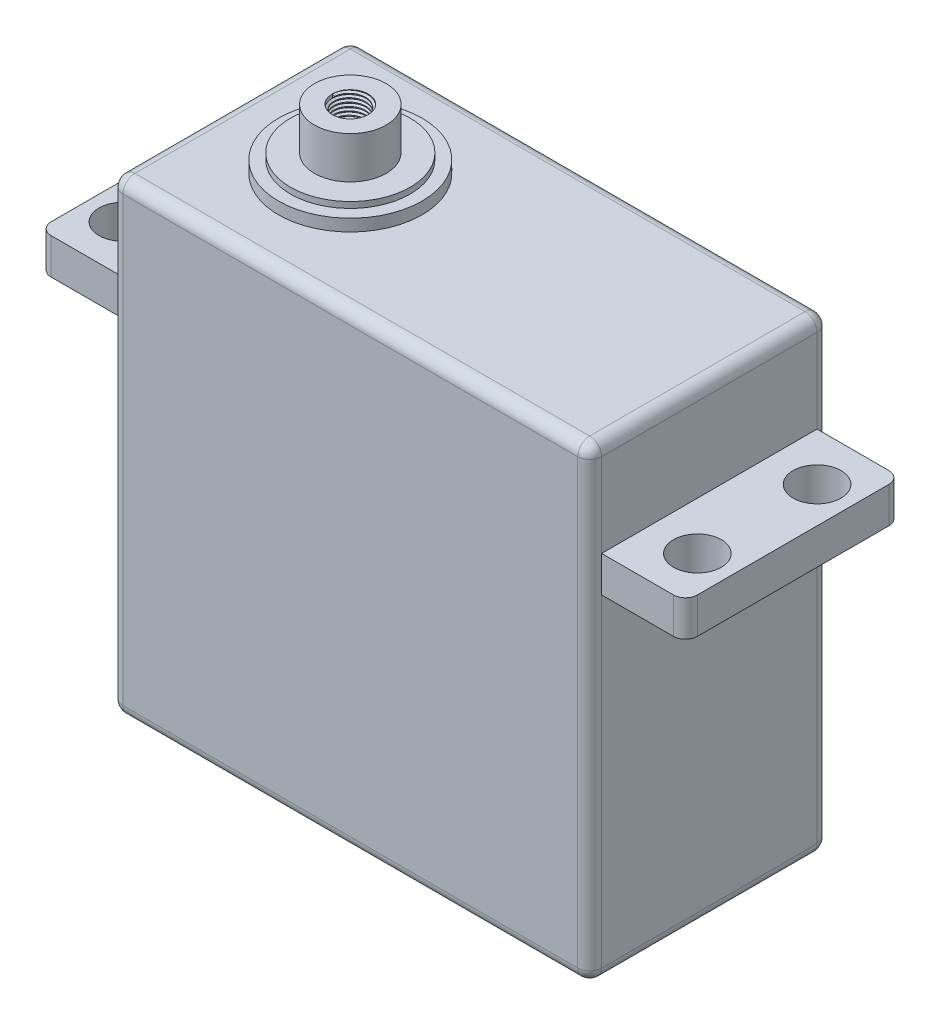
SolidWorks part; units mm, degrees
ref_plane "前视基准面" through (0, 0, 0) normal (0, 0, 1) x (1, 0, 0)
ref_plane "上视基准面" through (0, 0, 0) normal (0, 1, 0) x (1, 0, 0)
ref_plane "右视基准面" through (0, 0, 0) normal (1, 0, 0) x (0, 0, -1)
other "Configuration Table"
sketch "草图1" plane through (0, 0, 0) normal (0, 1, 0) x (1, 0, 0)
  line L1 (-20, -10) -> (20, -10)
  line L2 (-20, -10) -> (-20, 10)
  line L3 (-20, 10) -> (20, 10)
  line L4 (20, -10) -> (20, 10)
  line L5 (0, 10) -> (0, -10) construction
  line L6 (-20, 0) -> (20, 0) construction
  point P0 (0, 0)
  dimension "D1" = 40
  dimension "D2" = 20
extrude "凸台-拉伸1" add sketch "草图1" along normal blind 39
ref_plane "基准面1" through (0, 39, 0) normal (0, 1, 0) x (1, 0, 0)
sketch "草图3" plane through (0, 39, 0) normal (0, 1, 0) x (1, 0, 0)
  circle A0 centre (-10, 0) radius 6
  circle A1 centre (-10, 0) radius 5
  circle A2 centre (-10, 0) radius 3
  circle A3 centre (-10, 0) radius 1.5
ref_plane "基准面2" through (-20, 0, 0) normal (1, 0, 0) x (0, 0, -1)
ref_plane "基准面3" through (20, 0, 0) normal (1, 0, 0) x (0, 0, -1)
sketch "草图9" plane through (-20, 0, 0) normal (1, 0, 0) x (0, 0, -1)
  line L0 (-9, 28) -> (9, 28)
  line L2 (0, 31) -> (-9, 31)
  line L3 (-9, 31) -> (-9, 28)
  line L4 (9, 28) -> (9, 31)
  line L5 (9, 31) -> (0, 31)
extrude "凸台-拉伸6" add sketch "草图9" against normal blind 7 separate body
sketch "草图10" plane through (20, 0, 0) normal (1, 0, 0) x (0, 0, -1)
  line L0 (9, 28) -> (-9, 28)
  line L1 (0, 31) -> (9, 31)
  line L2 (9, 31) -> (9, 28)
  line L3 (-9, 28) -> (-9, 31)
  line L4 (-9, 31) -> (0, 31)
extrude "凸台-拉伸7" add sketch "草图10" along normal blind 7
ref_plane "基准面6" through (0, 31, 0) normal (0, 1, 0) x (1, 0, 0)
sketch "草图11" plane through (0, 31, 0) normal (0, 1, 0) x (1, 0, 0)
  circle A0 centre (-24, 5) radius 2
  circle A1 centre (-24, -5) radius 2
  circle A2 centre (24, 5) radius 2
  circle A3 centre (24, -5) radius 2
extrude "切除-拉伸2" cut sketch "草图11" against normal blind 3
fillet "圆角7" radius 1 8 edges at (-20, 0, 0) (0, 0, -10) (20, 0, 0) (0, 0, 10) (20, 19.5, -10) (20, 19.5, 10) (-20, 19.5, -10) (-20, 19.5, 10)
fillet "圆角8" radius 1 2 edges at (27, 29.5, -9) (27, 29.5, 9)
fillet "圆角9" radius 1 2 edges at (-27, 29.5, -9) (-27, 29.5, 9)
fillet "圆角10" radius 1 8 edges at (-19.7071, 39, 9.7071) (-19.7071, 39, -9.7071) (19.7071, 39, -9.7071) (19.7071, 39, 9.7071) (-20, 39, 0) (0, 39, -10) (20, 39, 0) (0, 39, 10)
extrude "凸台-拉伸12" add sketch "草图3" along normal blind 1 contours A0 A1 region at (-15.8303, 39, 0)
extrude "凸台-拉伸13" add sketch "草图3<3>" along normal blind 1.5 contours A1 A2 region at (-14.8586, 39, 0)
sketch "草图3<3>" plane through (0, 39, 0) normal (0, 1, 0) x (1, 0, 0) same geometry as "草图3"
extrude "凸台-拉伸14" add sketch "草图3<4>" along normal blind 5 contours A2 A3 region at (-12.9151, 39, 0)
sketch "草图3<4>" plane through (0, 39, 0) normal (0, 1, 0) x (1, 0, 0) same geometry as "草图3"
thread "螺纹线1" pitch 0.3175 method extrude profile "螺纹线轮廓1" start angle 0, offset 0, length 3.5, pitch 0.3175, diameter 3
ref_plane "基准面8" through (-11.5, 44, 0) normal (0, 0, 1) x (-1, 0, 0)
sketch "螺纹线轮廓1" plane through (-11.5, 44, 0) normal (0, 0, 1) x (-1, 0, 0)
  line L0 (0, 0) -> (0, 0.3175) construction
  line L11 (0, 0) -> (0, 0.2778)
  line L12 (0, 0.2778) -> (-0.1719, 0.1786)
  line L13 (-0.1719, 0.1786) -> (-0.1719, 0.0992)
  line L15 (-0.1719, 0.0992) -> (0, 0)
  line L17 (-0.1719, 0.1389) -> (0, 0.1389) construction
  point P2 (0, 0)
  dimension "Pitch" = 0.3175
  dimension "Profile_Angle" = 60
  dimension "Profile_Land" = 0.0794
  dimension "Profile_Height" = 0.1719
